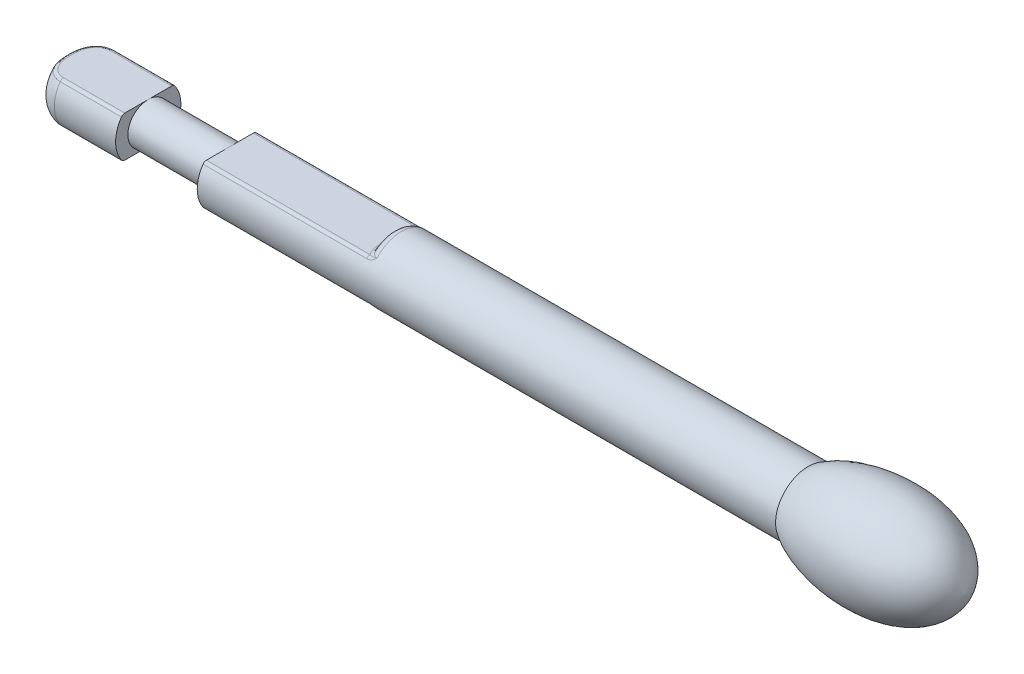
SolidWorks part; units mm, degrees
material "Tungsten"
ref_plane "Front Plane" through (0, 0, 0) normal (0, 0, 1) x (1, 0, 0)
ref_plane "Top Plane" through (0, 0, 0) normal (0, 1, 0) x (1, 0, 0)
ref_plane "Right Plane" through (0, 0, 0) normal (1, 0, 0) x (0, 0, -1)
sketch "Sketch1" plane through (0, 0, 0) normal (0, 0, 1) x (1, 0, 0)
  line L0 (0, 0) -> (0, 0.8)
  line L1 (0, 0.8) -> (2, 0.8)
  line L2 (2, 0.8) -> (2, 0.5)
  line L3 (2, 0.5) -> (4, 0.5)
  line L4 (4, 0.5) -> (4, 0.8)
  line L5 (4, 0.8) -> (18.167, 0.8)
  line L6 (0, 0) -> (22, 0) construction
  line L7 (0, 0) -> (22, 0)
  spline S0 degree 3 poles (18.167, 0.8) (19.116, 1.4337) (21.7178, 1.5479) (22, 0) knots 0 0 0 0 1 1 1 1
  dimension "D1" = 0.8
  dimension "D2" = 2
  dimension "D3" = 2
  dimension "D4" = 0.3
revolve "Revolve1" add sketch "Sketch1" angle 360 about L6
sketch "Sketch2" plane through (0, 0, 0) normal (-1, 0, 0) x (0, 0, 1)
  line L0 (0.6245, 0.5) -> (-0.6245, 0.5)
  line L1 (-0.6245, -0.5) -> (0.6245, -0.5)
  line L2 (-0.8, 0) -> (0.8, 0) construction
  arc A0 (-0.6245, -0.5) -> (0.6245, -0.5) centre (0, 0) ccw
  arc A1 (0.6245, 0.5) -> (-0.6245, 0.5) centre (0, 0) ccw
  circle A2 centre (0, 0) radius 0.8 construction
  dimension "D1" = 1
extrude "Cut-Extrude5" cut sketch "Sketch2" against normal blind 8
fillet "Fillet1" radius 0.5 1 edges at (0, 0, 0.8)
fillet "Fillet3" radius 0.2 2 edges at (8, -0.8, 0) (8, 0.8, 0)
fillet "Fillet4" radius 0.1 14 edges at (1.25, -0.5, 0.6245) (1.25, -0.5, -0.6245) (1.25, 0.5, -0.6245) (1.25, 0.5, 0.6245) (0.074, -0.5, 0.2561) (0.074, 0.5, -0.2561) (8.0554, -0.5, 0.5431) (8.0968, -0.5, -0.5873) (8.0968, 0.5, 0.5873) (8.0554, 0.5, -0.5431) (6.1, -0.5, 0.6245) (6.1, -0.5, -0.6245) (6.1, 0.5, 0.6245) (6.1, 0.5, -0.6245)
